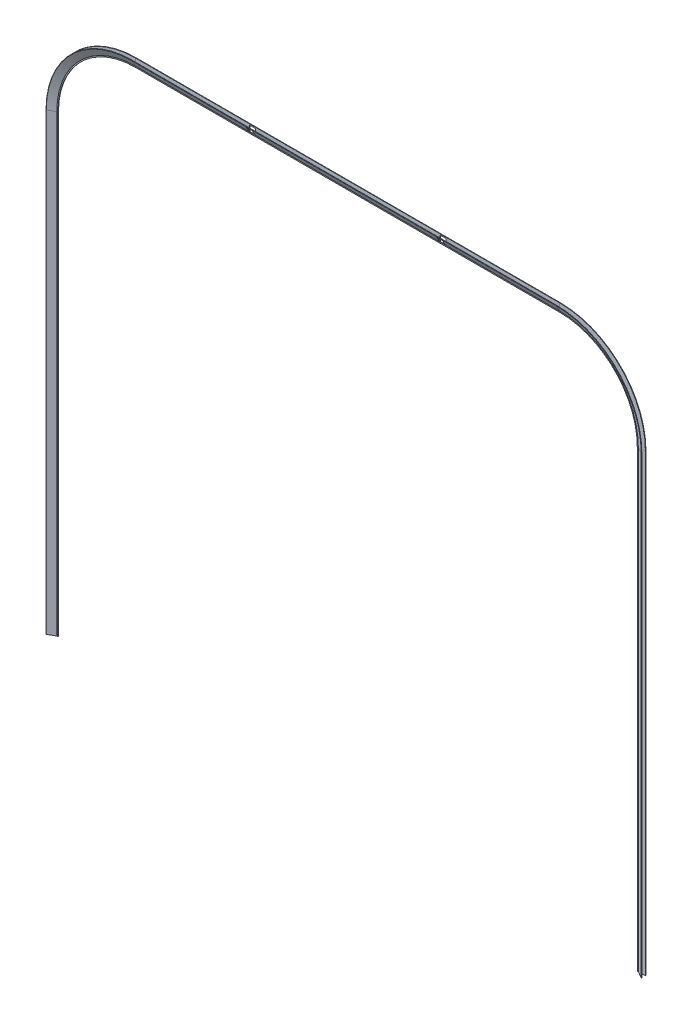
SolidWorks part; units mm, degrees
ref_plane "Front Plane" through (0, 0, 0) normal (0, 0, 1) x (1, 0, 0)
ref_plane "Top Plane" through (0, 0, 0) normal (0, 1, 0) x (1, 0, 0)
ref_plane "Right Plane" through (0, 0, 0) normal (1, 0, 0) x (0, 0, -1)
sketch "Sketch1" plane through (0, 0, 0) normal (0, 0, 1) x (1, 0, 0)
  line L0 (0, 0) -> (0, 1670)
  line L1 (285, 1955) -> (1845, 1955)
  line L2 (2130, 1670) -> (2130, 0)
  arc A0 (0, 1670) -> (285, 1955) centre (285, 1670) cw
  arc A1 (1845, 1955) -> (2130, 1670) centre (1845, 1670) cw
  dimension "D2" = 285
  dimension "D1" = 1670
  dimension "D3" = 1560
sketch "Sketch2" plane through (0, 0, 0) normal (0, 1, 0) x (1, 0, 0)
  line L0 (0, 0) -> (0, -2)
  line L1 (0, -2) -> (-4, -2)
  line L2 (-4, -2) -> (-30, -17.0111)
  line L3 (-30, -17.0111) -> (-30, -15.0111)
  line L4 (-30, -15.0111) -> (-7.4641, -2)
  line L5 (-7.4641, -2) -> (-30, -2)
  line L6 (-30, -2) -> (-30, 0)
  line L7 (-30, 0) -> (0, 0)
  dimension "D1" = 30
  dimension "D2" = 30
  dimension "D3" = 2
  dimension "D4" = 2
  dimension "D5" = 4
sweep "Sweep1" add profiles "Sketch2" path "Sketch1"
fillet "Fillet1" radius 1 20 edges at (2134, 835, 2) (2049.3539, 1874.3539, 2) (1065, 1959, 2) (80.6461, 1874.3539, 2) (2137.4641, 835, 2) (2051.8033, 1876.8033, 2) (1065, 1962.4641, 2) (78.1967, 1876.8033, 2) (-4, 835, 2) (-7.4641, 835, 2) (2160, 835, 15.0111) (2067.7386, 1892.7386, 15.0111) (1065, 1985, 15.0111) (62.2614, 1892.7386, 15.0111) (2160, 835, 17.0111) (2067.7386, 1892.7386, 17.0111) (1065, 1985, 17.0111) (62.2614, 1892.7386, 17.0111) (-30, 835, 15.0111) (-30, 835, 17.0111)
sketch "Sketch3" plane through (0, 0, 0) normal (0, 0, -1) x (-1, 0, 0)
  line L1 (-1426, 1981) -> (-1404, 1981)
  line L2 (-1426, 1981) -> (-1426, 1959)
  line L3 (-1426, 1959) -> (-1404, 1959)
  line L4 (-1404, 1981) -> (-1404, 1959)
  line L5 (-1845, 1955) -> (-1845, 1985) construction
  line L6 (-726, 1981) -> (-704, 1981)
  line L7 (-726, 1981) -> (-726, 1959)
  line L8 (-726, 1959) -> (-704, 1959)
  line L9 (-704, 1981) -> (-704, 1959)
  line L10 (-285, 1955) -> (-285, 1985) construction
  point P4 (-1732.5301, 2015.0565)
  point P10 (0, 0)
  point P14 (-1426, 1970)
  point P15 (-1845, 1970)
  dimension "D1" = 22
  dimension "D2" = 419
  dimension "D3" = 419
extrude "Cut-Extrude1" cut sketch "Sketch3" against normal through all
